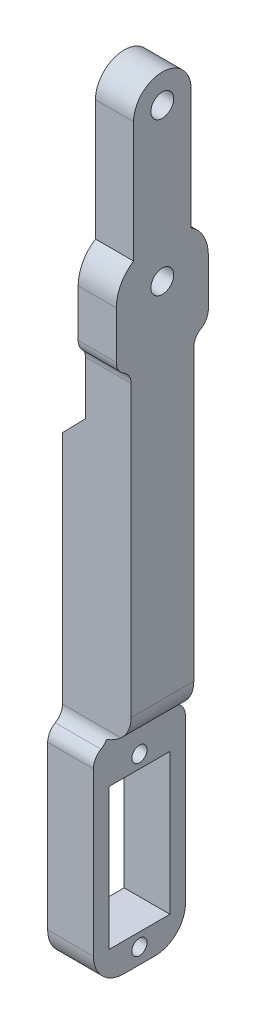
SolidWorks part; units mm, degrees
ref_plane "前视基准面" through (0, 0, 0) normal (0, 0, 1) x (1, 0, 0)
ref_plane "上视基准面" through (0, 0, 0) normal (0, 1, 0) x (1, 0, 0)
ref_plane "右视基准面" through (0, 0, 0) normal (1, 0, 0) x (0, 0, -1)
sketch "Sketch1" plane through (0, 0, 0) normal (1, 0, 0) x (0, 0, -1)
  circle A0 centre (2.9834, 10.8268) radius 7.75 construction
  circle A1 centre (2.9834, 10.8268) radius 6.25 construction
  circle A2 centre (2.9834, 18.5768) radius 0.8
  circle A3 centre (2.9834, 3.0768) radius 0.8
  circle A4 centre (-3.2666, 10.8268) radius 0.8
  circle A5 centre (9.2334, 10.8268) radius 0.8
  circle A6 centre (2.9834, 10.8268) radius 10
  circle A7 centre (2.9834, 10.8268) radius 3.3018
  dimension "D1" = 15.5
  dimension "D2" = 12.5
  dimension "D3" = 20
extrude "Boss-Extrude1" add sketch "Sketch1" along normal blind 1.5
sketch "Sketch2" plane through (0, 0, 0) normal (-1, 0, 0) x (0, 0, 1)
  line L0 (-2.9834, 10.8268) -> (-2.9834, 25.4318) construction
  line L2 (-12.9834, 90.8268) -> (7.0166, 90.8268) construction
  line L3 (-12.9834, 90.8268) -> (-12.9834, 10.8268) construction
  line L4 (-12.9834, 10.8268) -> (7.0166, 10.8268) construction
  line L5 (7.0166, 90.8268) -> (7.0166, 10.8268) construction
  line L6 (-12.9834, 90.8268) -> (7.0166, 10.8268) construction
  line L7 (-12.9834, 10.8268) -> (7.0166, 90.8268) construction
  line L8 (-15.5319, 90.8268) -> (9.5652, 90.8268)
  line L9 (-15.5319, 90.8268) -> (-15.5319, 10.8268)
  line L10 (-15.5319, 10.8268) -> (9.5652, 10.8268) construction
  line L11 (9.5652, 90.8268) -> (9.5652, 10.8268)
  line L12 (-15.5319, 90.8268) -> (9.5652, 10.8268) construction
  line L13 (-15.5319, 10.8268) -> (9.5652, 90.8268) construction
  circle A0 centre (-2.9834, 10.8268) radius 10 construction
  arc A1 (-12.9834, 10.8268) -> (7.0166, 10.8268) centre (-2.9834, 10.8268) cw construction
  circle A2 centre (-2.9834, 10.8268) radius 12.5485 construction
  circle A3 centre (-2.9834, 10.8268) radius 10
  arc A4 (-15.5319, 10.8268) -> (9.5652, 10.8268) centre (-2.9834, 10.8268) ccw
  circle A5 centre (-2.9834, 10.8268) radius 0.6321 construction
  point P1 (-2.9834, 50.8268)
  point P12 (-2.9834, 50.8268)
  dimension "D1" = 0
  dimension "D2" = 80
extrude "Boss-Extrude2" add sketch "Sketch2" against normal blind 9
sketch "Sketch3" plane through (9, 0, 0) normal (1, 0, 0) x (0, 0, -1)
  line L0 (2.9834, 95.8916) -> (2.9834, 22.8694) construction
  line L1 (-9.5652, 90.8268) -> (15.5319, 90.8268) construction
  line L3 (-3.0511, 36.1504) -> (-3.0511, 97.5726)
  line L4 (-3.0511, 97.5726) -> (-16.389, 97.5726)
  line L5 (-16.389, 97.5726) -> (-16.389, 8.1411)
  line L6 (-16.389, 8.1411) -> (-9.5652, 10.8268)
  line L7 (22.3558, 8.1411) -> (15.5319, 10.8268)
  line L8 (22.3558, 97.5726) -> (22.3558, 8.1411)
  line L9 (9.0179, 97.5726) -> (22.3558, 97.5726)
  line L10 (9.0179, 36.1504) -> (9.0179, 97.5726)
  circle A0 centre (2.9834, 85.8268) radius 1.5
  spline S0 degree 3 poles (-9.5652, 10.8268) (-9.6442, 15.1222) (-6.9162, 23.507) (-3.4283, 31.5617) (-3.0511, 36.1504) knots 0 0 0 0 0.482385 1 1 1 1
  spline S1 degree 3 poles (15.5319, 10.8268) (15.611, 15.1222) (12.883, 23.507) (9.395, 31.5617) (9.0179, 36.1504) knots 0 0 0 0 0.482385 1 1 1 1
  dimension "D1" = 5
extrude "Cut-Extrude1" cut sketch "Sketch3" against normal through all both and the other way through all
fillet "Fillet1" radius 5 2 edges at (4.5, 90.8268, -9.0179) (4.5, 90.8268, 3.0511)
sketch "Sketch4" plane through (9, 0, 0) normal (1, 0, 0) x (0, 0, -1)
  line L0 (2.9834, 85.8268) -> (2.9834, 105.8268) construction
  line L1 (-0.7887, 85.8268) -> (-0.7887, 105.8268)
  line L2 (6.7554, 85.8268) -> (6.7554, 105.8268)
  arc A0 (-0.7887, 85.8268) -> (6.7554, 85.8268) centre (2.9834, 85.8268) ccw
  arc A1 (6.7554, 105.8268) -> (-0.7887, 105.8268) centre (2.9834, 105.8268) ccw
  circle A2 centre (2.9834, 105.8268) radius 1.5
  circle A3 centre (2.9834, 85.8268) radius 1.5
  point P3 (2.9834, 95.8268)
  dimension "D1" = 20
extrude "Boss-Extrude3" add sketch "Sketch4" against normal blind 5
sketch "Sketch5" plane through (0, 0, 0) normal (-1, 0, 0) x (0, 0, 1)
  line L0 (3.0511, 66.6904) -> (-0.5206, 90.6184)
  line L1 (3.0511, 36.1504) -> (3.0511, 85.8268) construction
  line L2 (-0.5206, 90.6184) -> (8.9944, 90.6184)
  line L3 (8.9944, 90.6184) -> (4.4528, 66.6904)
  line L4 (4.4528, 66.6904) -> (3.0511, 66.6904)
  line L5 (-9.0179, 66.6904) -> (-5.4462, 90.6184)
  line L6 (-9.0179, 85.8268) -> (-9.0179, 36.1504) construction
  line L7 (-5.4462, 90.6184) -> (-12.4698, 95.2806)
  line L8 (-12.4698, 95.2806) -> (-31.4476, 66.6904)
  line L9 (-31.4476, 66.6904) -> (-9.0179, 66.6904)
  arc A0 (0.7887, 90.0108) -> (-1.9489, 90.8268) centre (-1.9489, 85.8268) ccw construction
  arc A1 (-4.0179, 90.8268) -> (-6.7554, 90.0108) centre (-4.0179, 85.8268) ccw construction
  dimension "D1" = 0
extrude "Cut-Extrude2" cut sketch "Sketch5" against normal up to surface (4 mm away) up to face at (4, 96.25, -2.9834)
fillet "Fillet3" radius 2 2 edges at (2, 90.6184, -5.4462) (2, 90.6184, -0.5206)
sketch "Sketch6" plane through (9, 0, 0) normal (1, 0, 0) x (0, 0, -1)
  line L0 (9.0179, 36.1504) -> (9.0179, 28.2815) construction
  line L2 (-3.0511, 36.1504) -> (9.0179, 36.1504)
  line L3 (-3.0511, 36.1504) -> (-3.0511, 0)
  line L4 (-3.0511, 0) -> (9.0179, 0)
  line L5 (9.0179, 36.1504) -> (9.0179, 0)
extrude "Boss-Extrude4" add sketch "Sketch6" against normal up to surface (9 mm away) up to face at (0, 85.8268, -4.4834)
sketch "Sketch7" plane through (9, 0, 0) normal (1, 0, 0) x (0, 0, -1)
  line L0 (-3.0511, 36.1504) -> (-3.0511, -1.9848) construction
  line L1 (-3.0511, -1.9848) -> (-23.4996, -1.9848)
  line L2 (-23.4996, -1.9848) -> (-3.0511, 36.1504)
  line L3 (9.0179, 36.1504) -> (9.0179, -7.6597) construction
  line L4 (9.0179, -7.6597) -> (33.092, 2.7443)
  line L5 (33.092, 2.7443) -> (9.0179, 36.1504)
  line L6 (-3.0511, 36.1504) -> (-3.0511, 6.6932)
  line L7 (-3.0511, 6.6932) -> (9.0179, 6.6932)
  line L8 (9.0179, 6.6932) -> (9.0179, 36.1504)
  line L9 (-3.0511, -1.9848) -> (9.0179, -7.6597)
extrude "Cut-Extrude3" cut sketch "Sketch7" against normal through all both and the other way through all
sketch "Sketch8" plane through (9, 0, 0) normal (1, 0, 0) x (0, 0, -1)
  line L0 (2.9834, 88.9737) -> (2.9834, 82.9384) construction
  line L1 (-3.0511, 6.6932) -> (9.0179, 6.6932) construction
  line L2 (6.9834, 28.9432) -> (-1.0166, 28.9432)
  line L3 (6.9834, 28.9432) -> (6.9834, 10.4432)
  line L4 (6.9834, 10.4432) -> (-1.0166, 10.4432)
  line L5 (-1.0166, 28.9432) -> (-1.0166, 10.4432)
  line L6 (6.9834, 28.9432) -> (-1.0166, 10.4432) construction
  line L7 (6.9834, 10.4432) -> (-1.0166, 28.9432) construction
  line L8 (3.7847, 30.6482) -> (2.1821, 30.6482) construction
  line L9 (3.7847, 30.6482) -> (3.7847, 8.7382) construction
  line L10 (3.7847, 8.7382) -> (2.1821, 8.7382) construction
  line L11 (2.1821, 30.6482) -> (2.1821, 8.7382) construction
  line L12 (3.7847, 30.6482) -> (2.1821, 8.7382) construction
  line L13 (3.7847, 8.7382) -> (2.1821, 30.6482) construction
  circle A0 centre (2.9834, 30.6482) radius 1
  circle A1 centre (2.9834, 8.7382) radius 1
  circle A2 centre (2.9834, 85.8268) radius 0.5708 construction
  point P1 (2.9834, 19.6932)
  point P8 (2.9834, 19.6932)
  dimension "D4" = 13
  dimension "D1" = 8
  dimension "D2" = 18.5
  dimension "D3" = 21.91
  dimension "D5" = 0
  dimension "D6" = 0
extrude "Cut-Extrude4" cut sketch "Sketch8" against normal through all both and the other way through all
fillet "Fillet4" radius 4 2 edges at (4.5, 6.6932, -9.0179) (4.5, 6.6932, 3.0511)
sketch "Sketch9" plane through (9, 0, 0) normal (1, 0, 0) x (0, 0, -1)
  line L1 (-8.9789, -0.9142) -> (15.4035, -0.9142)
  line L2 (-8.9789, -0.9142) -> (-8.9789, 34.4574)
  line L3 (-8.9789, 34.4574) -> (15.4035, 34.4574)
  line L4 (15.4035, -0.9142) -> (15.4035, 34.4574)
extrude "Cut-Extrude5" cut sketch "Sketch9" against normal blind 3
fillet "Fillet5" radius 4 1 edges at (9, 34.4574, -2.9834)
sketch "Sketch10" plane through (0, 0, 0) normal (-1, 0, 0) x (0, 0, 1)
  circle A0 centre (-2.9834, 85.8268) radius 20.0653
extrude "Cut-Extrude6" cut sketch "Sketch10" against normal blind 3
sketch "Sketch11" plane through (0, 0, 0) normal (-1, 0, 0) x (0, 0, 1)
  line L0 (-3.0031, 100.8499) -> (-3.0031, 107.7727) construction
  line L1 (-9.0179, 76.2586) -> (-9.0179, 35.3573) construction
  line L2 (-7.11, 76.2586) -> (-7.11, 35.3573)
  line L3 (-10.9258, 76.2586) -> (-10.9258, 35.3573)
  line L4 (-9.0179, 66.6904) -> (-9.0179, 10.6932) construction
  line L5 (-9.0179, 66.6904) -> (-9.0179, 85.8268) construction
  line L6 (3.0116, 76.2586) -> (3.0116, 35.3573) construction
  line L7 (1.1037, 76.2586) -> (1.1037, 35.3573)
  line L8 (4.9195, 76.2586) -> (4.9195, 35.3573)
  arc A0 (-7.11, 76.2586) -> (-10.9258, 76.2586) centre (-9.0179, 76.2586) ccw
  arc A1 (-10.9258, 35.3573) -> (-7.11, 35.3573) centre (-9.0179, 35.3573) ccw
  arc A2 (1.1037, 76.2586) -> (4.9195, 76.2586) centre (3.0116, 76.2586) cw
  arc A3 (4.9195, 35.3573) -> (1.1037, 35.3573) centre (3.0116, 35.3573) cw
  point P5 (-9.0179, 55.8079)
  point P19 (3.0116, 55.8079)
extrude "Cut-Extrude7" cut sketch "Sketch11" against normal through all both and the other way through all
fillet "Fillet6" radius 2 4 edges at (3, 33.4494, -9.0179) (3, 33.4498, 3.0511) (6.5, 78.1665, -9.0179) (6.5, 78.1661, 3.0511)
chamfer "Chamfer1" distance 3 angle 45 1 edges at (3, 65.7614, -3.0035)
